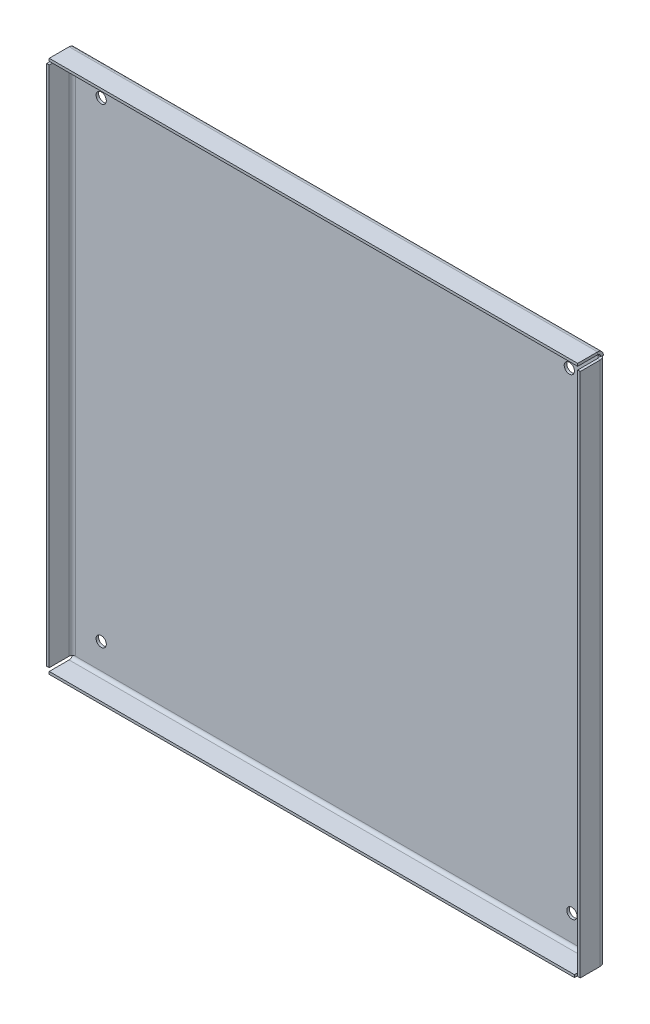
SolidWorks part; units mm, degrees
note: The reader was unsure of these and kept them because the rebuilt part matched: flange length of "Edge-Flange1", "Edge-Flange2", "Edge-Flange3", "Edge-Flange4".
material "Galvanized Steel"
ref_plane "Front Plane" through (0, 0, 0) normal (0, 0, 1) x (1, 0, 0)
ref_plane "Top Plane" through (0, 0, 0) normal (0, 1, 0) x (1, 0, 0)
ref_plane "Right Plane" through (0, 0, 0) normal (1, 0, 0) x (0, 0, -1)
sketch "Sketch1" plane through (0, 0, 0) normal (0, 0, 1) x (1, 0, 0)
  line L1 (207, 205) -> (-205, 205)
  line L2 (207, 205) -> (207, -207)
  line L3 (207, -207) -> (-205, -207)
  line L4 (-205, 205) -> (-205, -207)
  dimension "D1" = 412
  dimension "D2" = 412
base flange "Base-Flange1" sketch "Sketch1" thickness 2 reverse thickness direction no parameters "D1"=0.7366
edge flange "Edge-Flange1" sketch "Sketch8" flange angle 90 flange length 20 flange position material outside bend radius 2.5 thickness 2 relief rectangular parameters "D6"=10
sketch "Sketch8" plane through (0, 205, 0) normal (0, -1, 0) x (1, 0, 0)
  line L1 (207, 0) -> (-205, 0) construction
  line L2 (-205, 0) -> (-205, 18)
  line L3 (-205, 18) -> (207, 18)
  line L4 (207, 18) -> (207, 0)
  line L5 (207, 0) -> (-205, 0)
bend "EdgeBend1" bend radius 2.5 bend angle 90 parameters "D5"=1
edge flange "Edge-Flange2" sketch "Sketch11" flange angle 90 flange length 20 flange position material outside bend radius 2.5 thickness 2 relief none parameters "D6"=10
sketch "Sketch11" plane through (207, 0, 0) normal (-1, 0, 0) x (0, -1, 0)
  line L1 (207, 0) -> (-202.5, 0) construction
  line L2 (-202.5, 0) -> (-202.5, 18)
  line L3 (-202.5, 18) -> (207, 18)
  line L4 (207, 18) -> (207, 0)
  line L5 (207, 0) -> (-202.5, 0)
bend "EdgeBend2" bend radius 2.5 bend angle 90 parameters "D5"=2
edge flange "Edge-Flange3" sketch "Sketch14" flange angle 90 flange length 20 flange position material outside bend radius 2.5 thickness 2 relief none parameters "D6"=10
sketch "Sketch14" plane through (0, -207, 0) normal (0, 1, 0) x (-1, 0, 0)
  line L1 (205, 0) -> (-204.5, 0) construction
  line L2 (-204.5, 0) -> (-204.5, 18)
  line L3 (-204.5, 18) -> (205, 18)
  line L4 (205, 18) -> (205, 0)
  line L5 (205, 0) -> (-204.5, 0)
bend "EdgeBend3" bend radius 2.5 bend angle 90 parameters "D5"=3
edge flange "Edge-Flange4" sketch "Sketch17" flange angle 90 flange length 20 flange position material outside bend radius 2.5 thickness 2 relief none parameters "D6"=10
sketch "Sketch17" plane through (-205, 0, 0) normal (1, 0, 0) x (0, 1, 0)
  line L1 (202.5, 0) -> (-204.5, 0) construction
  line L2 (-204.5, 0) -> (-204.5, 18)
  line L3 (-204.5, 18) -> (202.5, 18)
  line L4 (202.5, 18) -> (202.5, 0)
  line L5 (202.5, 0) -> (-204.5, 0)
bend "EdgeBend4" bend radius 2.5 bend angle 90 parameters "D5"=4
sketch "Sketch18" plane through (0, 0, -2) normal (0, 0, -1) x (-1, 0, 0)
  line L0 (-204.5, 202.5) -> (-204.5, -204.5) construction
  line L1 (-204.5, -204.5) -> (202.5, -204.5) construction
  line L2 (202.5, -204.5) -> (202.5, 202.5) construction
  line L3 (202.5, 202.5) -> (-204.5, 202.5) construction
  circle A0 centre (-184.5, -184.5) radius 4
  circle A1 centre (182.5, -184.5) radius 4
  circle A2 centre (182.5, 182.5) radius 4
  circle A3 centre (-182.5, 182.5) radius 4
  dimension "D1" = 20
  dimension "D2" = 20
  dimension "D3" = 8
  dimension "D4" = 20
  dimension "D5" = 20
  dimension "D6" = 8
  dimension "D7" = 20
  dimension "D8" = 20
  dimension "D9" = 8
  dimension "D11" = 8
  dimension "D10" = 20
extrude "Cut-Extrude1" cut sketch "Sketch18" against normal blind 10 normal cut yes
sketch "Bend-Lines1" [suppressed] plane through (0, 0, 0) normal (0, 1, 0) x (1, 0, 0)
sketch "Bounding-Box1" [suppressed] plane through (0, 0, 0) normal (0, 1, 0) x (1, 0, 0)
sheet metal parameters "Sheet-Metal1" thickness 2 parameters "D1"=0.7366
flat pattern "Flat-Pattern1" [suppressed]
sketch "Bend-Lines2" plane through (0, 0, 0) normal (0, 1, 0) x (1, 0, 0)
sketch3d "Bounding-Box2" [suppressed]
  line L0 (205, -205, 0) -> (-205, -205, 0) construction
  line L1 (205, 205, 0) -> (-205, 205, 0) construction
  line L2 (205, -205, 0) -> (205, 205, 0) construction
  line L3 (-205, -205, 0) -> (-205, 205, 0) construction
sheet metal parameters "Sheet-Metal2" thickness 2 parameters "D1"=0.7366
flat pattern "Flat-Pattern1"
sketch "Bend-Lines2" plane through (0, 0, 0) normal (0, 0, 1) x (1, 0, 0)
  line L0 (205, 205.2489) -> (-205, 205.2489) construction
  line L1 (205, 205.2489) -> (-205, 205.2489) construction
sketch3d "Bounding-Box2" [suppressed]
  line L0 (205, 223.4978, 0) -> (205, -205, 0) construction
  line L1 (-205, 223.4978, 0) -> (-205, -205, 0) construction
  line L2 (205, 223.4978, 0) -> (-205, 223.4978, 0) construction
  line L3 (205, -205, 0) -> (-205, -205, 0) construction
bend of the flat pattern "Flatten-<EdgeBend1>1"
sheet metal parameters "Sheet-Metal3" thickness 2 parameters "D1"=0.7366
flat pattern "Flat-Pattern1"
sketch "Bend-Lines2" plane through (0, 0, 0) normal (0, 0, 1) x (1, 0, 0)
  line L0 (205, 205.2489) -> (-205, 205.2489) construction
  line L1 (205, 205.2489) -> (-205, 205.2489) construction
  line L2 (205.2489, -205) -> (205.2489, 202.5) construction
  line L3 (205.2489, -205) -> (205.2489, 202.5) construction
sketch3d "Bounding-Box2" [suppressed]
  line L0 (-205, -205, 0) -> (223.4978, -205, 0) construction
  line L1 (-205, 223.4978, 0) -> (223.4978, 223.4978, 0) construction
  line L2 (-205, -205, 0) -> (-205, 223.4978, 0) construction
  line L3 (223.4978, -205, 0) -> (223.4978, 223.4978, 0) construction
bend of the flat pattern "Flatten-<EdgeBend1>1"
bend of the flat pattern "Flatten-<EdgeBend2>1"
sheet metal parameters "Sheet-Metal4" thickness 2 parameters "D1"=0.7366
flat pattern "Flat-Pattern1"
sketch "Bend-Lines2" plane through (0, 0, 0) normal (0, 0, 1) x (1, 0, 0)
  line L0 (205, 205.2489) -> (-205, 205.2489) construction
  line L1 (205, 205.2489) -> (-205, 205.2489) construction
  line L2 (205.2489, -205) -> (205.2489, 202.5) construction
  line L3 (205.2489, -205) -> (205.2489, 202.5) construction
  line L4 (-205, -205.2489) -> (202.5, -205.2489) construction
  line L5 (-205, -205.2489) -> (202.5, -205.2489) construction
sketch3d "Bounding-Box2" [suppressed]
  line L0 (223.4978, 223.4978, 0) -> (223.4978, -223.4978, 0) construction
  line L1 (-205, 223.4978, 0) -> (-205, -223.4978, 0) construction
  line L2 (223.4978, 223.4978, 0) -> (-205, 223.4978, 0) construction
  line L3 (223.4978, -223.4978, 0) -> (-205, -223.4978, 0) construction
bend of the flat pattern "Flatten-<EdgeBend1>1"
bend of the flat pattern "Flatten-<EdgeBend2>1"
bend of the flat pattern "Flatten-<EdgeBend3>1"
sheet metal parameters "Sheet-Metal5" thickness 2 parameters "D1"=0.7366
flat pattern "Flat-Pattern1"
sketch "Bend-Lines2" plane through (0, 0, 0) normal (0, 0, 1) x (1, 0, 0)
  line L0 (205, 205.2489) -> (-205, 205.2489) construction
  line L1 (205, 205.2489) -> (-205, 205.2489) construction
  line L2 (205.2489, -205) -> (205.2489, 202.5) construction
  line L3 (205.2489, -205) -> (205.2489, 202.5) construction
  line L4 (-205, -205.2489) -> (202.5, -205.2489) construction
  line L5 (-205, -205.2489) -> (202.5, -205.2489) construction
  line L6 (-205.2489, 202.5) -> (-205.2489, -202.5) construction
  line L7 (-205.2489, 202.5) -> (-205.2489, -202.5) construction
sketch3d "Bounding-Box2" [suppressed]
  line L0 (-223.4978, -223.4978, 0) -> (223.4978, -223.4978, 0) construction
  line L1 (-223.4978, 223.4978, 0) -> (223.4978, 223.4978, 0) construction
  line L2 (-223.4978, -223.4978, 0) -> (-223.4978, 223.4978, 0) construction
  line L3 (223.4978, -223.4978, 0) -> (223.4978, 223.4978, 0) construction
bend of the flat pattern "Flatten-<EdgeBend1>1"
bend of the flat pattern "Flatten-<EdgeBend2>1"
bend of the flat pattern "Flatten-<EdgeBend3>1"
bend of the flat pattern "Flatten-<EdgeBend4>1"
sheet metal parameters "Sheet-Metal6" thickness 2 parameters "D1"=0.7366
flat pattern "Flat-Pattern1"
sketch "Bend-Lines2" plane through (0, 0, 0) normal (0, 0, 1) x (1, 0, 0)
  line L0 (207, 205.2489) -> (-205, 205.2489) construction
  line L1 (207, 205.2489) -> (-205, 205.2489) construction
  line L2 (207.2489, -207) -> (207.2489, 202.5) construction
  line L3 (207.2489, -207) -> (207.2489, 202.5) construction
  line L4 (-205, -207.2489) -> (204.5, -207.2489) construction
  line L5 (-205, -207.2489) -> (204.5, -207.2489) construction
  line L6 (-205.2489, 202.5) -> (-205.2489, -204.5) construction
  line L7 (-205.2489, 202.5) -> (-205.2489, -204.5) construction
sketch3d "Bounding-Box2" [suppressed]
  line L0 (-223.4978, -225.4978, 0) -> (225.4978, -225.4978, 0) construction
  line L1 (-223.4978, 223.4978, 0) -> (225.4978, 223.4978, 0) construction
  line L2 (-223.4978, -225.4978, 0) -> (-223.4978, 223.4978, 0) construction
  line L3 (225.4978, -225.4978, 0) -> (225.4978, 223.4978, 0) construction
bend of the flat pattern "Flatten-<EdgeBend1>1"
bend of the flat pattern "Flatten-<EdgeBend2>1"
bend of the flat pattern "Flatten-<EdgeBend3>1"
bend of the flat pattern "Flatten-<EdgeBend4>1"
